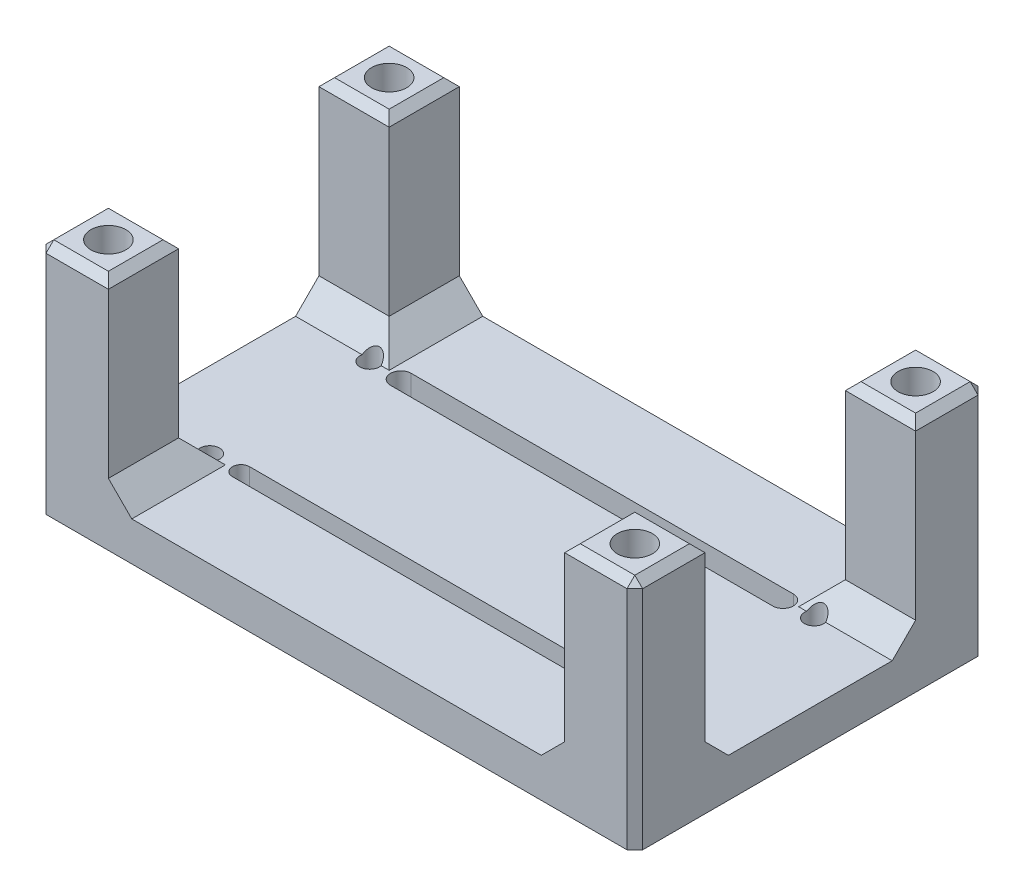
SolidWorks part; units mm, degrees
ref_plane "Front Plane" through (0, 0, 0) normal (0, 0, 1) x (1, 0, 0)
ref_plane "Top Plane" through (0, 0, 0) normal (0, 1, 0) x (1, 0, 0)
ref_plane "Right Plane" through (0, 0, 0) normal (1, 0, 0) x (0, 0, -1)
sketch "Sketch1" plane through (0, 0, 0) normal (0, 1, 0) x (1, 0, 0)
  line L0 (9.75, 32.75) -> (66.75, 32.75) construction
  line L1 (0, 0) -> (76.5, 0)
  line L2 (0, 0) -> (0, 45)
  line L3 (0, 45) -> (76.5, 45)
  line L4 (76.5, 0) -> (76.5, 45)
  line L5 (66.75, 32.75) -> (66.75, 12.25) construction
  line L6 (66.75, 12.25) -> (9.75, 12.25) construction
  line L7 (9.75, 12.25) -> (9.75, 32.75) construction
  line L8 (13.75, 32.75) -> (62.75, 32.75) construction
  line L9 (13.75, 34.0805) -> (62.75, 34.0805)
  line L10 (13.75, 31.4195) -> (62.75, 31.4195)
  line L11 (13.75, 12.25) -> (62.75, 12.25) construction
  line L12 (13.75, 13.3523) -> (62.75, 13.3523)
  line L13 (13.75, 11.1477) -> (62.75, 11.1477)
  line L14 (9.75, 22.5) -> (0, 22.5) construction
  line L15 (38.25, 32.75) -> (38.25, 45) construction
  circle A0 centre (9.75, 32.75) radius 1.25
  circle A1 centre (9.75, 12.25) radius 1.25
  circle A2 centre (66.75, 12.25) radius 1.25
  circle A3 centre (66.75, 32.75) radius 1.25
  arc A4 (13.75, 34.0805) -> (13.75, 31.4195) centre (13.75, 32.75) ccw
  arc A5 (62.75, 31.4195) -> (62.75, 34.0805) centre (62.75, 32.75) ccw
  arc A6 (13.75, 13.3523) -> (13.75, 11.1477) centre (13.75, 12.25) ccw
  arc A7 (62.75, 11.1477) -> (62.75, 13.3523) centre (62.75, 12.25) ccw
  point P15 (38.25, 32.75)
  point P20 (38.25, 12.25)
  dimension "D2" = 2.5
  dimension "D3" = 2.5
  dimension "D4" = 2.5
  dimension "D5" = 2.5
  dimension "D1" = 20.5
  dimension "D6" = 45
  dimension "D7" = 76.5
  dimension "D8" = 57
  dimension "D9" = 4
  dimension "D10" = 4
  dimension "D11" = 4
  dimension "D12" = 4
extrude "Boss-Extrude1" add sketch "Sketch1" along normal blind 5
sketch "Sketch2" plane through (0, 5, 0) normal (0, 1, 0) x (1, 0, 0)
  line L0 (4.5, 45) -> (4.5, 36) construction
  line L1 (0, 45) -> (9, 45)
  line L2 (0, 45) -> (0, 36)
  line L3 (0, 36) -> (9, 36)
  line L4 (9, 45) -> (9, 36)
  line L5 (0, 0) -> (9, 0)
  line L6 (0, 0) -> (0, 9)
  line L7 (0, 9) -> (9, 9)
  line L8 (9, 0) -> (9, 9)
  line L9 (76.5, 0) -> (67.5, 0)
  line L10 (76.5, 0) -> (76.5, 9)
  line L11 (76.5, 9) -> (67.5, 9)
  line L12 (67.5, 0) -> (67.5, 9)
  line L13 (76.5, 45) -> (67.5, 45)
  line L14 (76.5, 45) -> (76.5, 36)
  line L15 (76.5, 36) -> (67.5, 36)
  line L16 (67.5, 45) -> (67.5, 36)
  line L17 (0, 40.5) -> (9, 40.5) construction
  line L18 (67.5, 40.5) -> (76.5, 40.5) construction
  line L19 (72, 36) -> (72, 45) construction
  line L20 (72, 9) -> (72, 0) construction
  line L21 (67.5, 4.5) -> (76.5, 4.5) construction
  line L22 (0, 4.5) -> (9, 4.5) construction
  line L23 (4.5, 9) -> (4.5, 0) construction
  circle A0 centre (4.5, 4.5) radius 2.25
  circle A1 centre (4.5, 40.5) radius 2.25
  circle A2 centre (72, 4.5) radius 2.25
  circle A3 centre (72, 40.5) radius 2.25
  dimension "D1" = 4.5
  dimension "D2" = 4.5
  dimension "D3" = 4.5
  dimension "D4" = 4.5
  dimension "D5" = 9
  dimension "D6" = 9
  dimension "D7" = 9
  dimension "D8" = 9
  dimension "D9" = 9
  dimension "D10" = 9
  dimension "D11" = 9
  dimension "D12" = 9
extrude "Boss-Extrude2" add sketch "Sketch2" along normal blind 25
chamfer "Chamfer1" distance 1 angle 45 20 edges at (76.5, 15, 0) (72, 30, 0) (76.5, 30, -4.5) (67.5, 30, -4.5) (72, 30, -9) (76.5, 15, -45) (72, 30, -36) (76.5, 30, -40.5) (72, 30, -45) (67.5, 30, -40.5) (0, 15, -45) (4.5, 30, -45) (9, 30, -40.5) (4.5, 30, -36) (0, 30, -40.5) (0, 15, 0) (4.5, 30, 0) (0, 30, -4.5) (9, 30, -4.5) (4.5, 30, -9)
chamfer "Chamfer2" distance 3 angle 45 8 edges at (72, 5, -36) (67.5, 5, -40.5) (72, 5, -9) (67.5, 5, -4.5) (9, 5, -4.5) (4.5, 5, -9) (4.5, 5, -36) (9, 5, -40.5)
